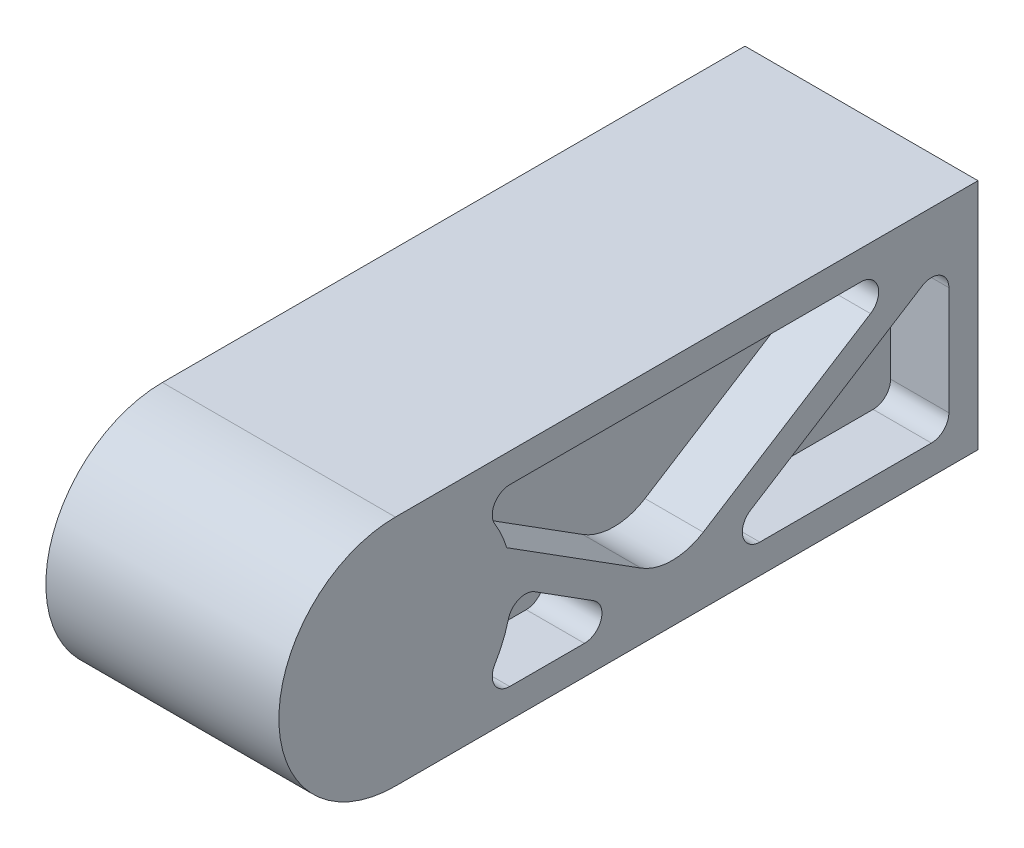
SolidWorks part; units mm, degrees
ref_plane "Front Plane" through (0, 0, 0) normal (0, 0, 1) x (1, 0, 0)
ref_plane "Top Plane" through (0, 0, 0) normal (0, 1, 0) x (1, 0, 0)
ref_plane "Right Plane" through (0, 0, 0) normal (1, 0, 0) x (0, 0, -1)
sketch "Sketch1" plane through (0, 0, 0) normal (1, 0, 0) x (0, 0, -1)
  line L0 (0, 0) -> (-50, 0) construction
  line L1 (-50, -20) -> (50, -20)
  line L2 (-50, -20) -> (-50, 20) construction
  line L3 (-50, 20) -> (50, 20)
  line L4 (50, -20) -> (50, 20)
  line L5 (-50, -20) -> (50, 20) construction
  line L6 (-50, 20) -> (50, -20) construction
  arc A0 (-50, 20) -> (-50, -20) centre (-50, 0) ccw
  point P0 (0, 0)
  point P9 (-47.349, 0)
  dimension "D1" = 100
  dimension "D2" = 40
extrude "Boss-Extrude1" add sketch "Sketch1" along normal blind 20 and the other way blind 20
sketch "Sketch2" plane through (20, 0, 0) normal (1, 0, 0) x (0, 0, -1)
  line L3 (45, 15) -> (-2.5, -15)
  line L4 (-2.5, -15) -> (-50, 15)
  line L5 (43.665, 17.1137) -> (-2.5, -12.0431)
  line L6 (45, -15) -> (45, 15)
  line L7 (-50, -15) -> (45, -15)
  line L8 (45, 15) -> (-50, 15)
  line L9 (45, -15) -> (45, 15)
  line L10 (-50, -15) -> (45, -15)
  line L11 (45, 15) -> (-50, 15)
  line L12 (-2.5, -12.0431) -> (-48.665, 17.1137)
  line L13 (46.335, 12.8863) -> (-2.5, -17.9569)
  line L14 (-2.5, -17.9569) -> (-51.335, 12.8863)
  circle A0 centre (-50, 0) radius 20
  dimension "D1" = 5
  dimension "D2" = 2.5
  dimension "D3" = 2.5
extrude "Cut-Extrude1" cut sketch "Sketch2" against normal blind 10 contours A0 L12 L5 L11 | L9 L13 L10 | A0 L10 L14 region at (20, -5.9856, -30.7272) region at (20, 5.754, 1.1181) region at (20, -10.3863, 23.9176)
sketch "Sketch4" plane through (-20, 0, 0) normal (-1, 0, 0) x (0, 0, 1)
  line L2 (7.1817, -15) -> (36.7712, -15)
  line L3 (2.5, -12.0431) -> (30.8852, 5.8844)
  line L4 (-40.3183, 15) -> (2.5, -12.0431)
  line L5 (36.7712, 15) -> (-40.3183, 15)
  line L6 (2.5, -12.0431) -> (30.8852, 5.8844)
  line L7 (-40.3183, 15) -> (2.5, -12.0431)
  line L8 (36.7712, 15) -> (-40.3183, 15)
  line L9 (30.0085, -0.5831) -> (7.1817, -15)
  line L10 (7.1817, -15) -> (36.7712, -15)
  line L11 (30.0085, -0.5831) -> (7.1817, -15)
  line L13 (-45, 12.0431) -> (-45, -15)
  line L14 (-2.1817, -15) -> (-45, 12.0431)
  line L15 (-45, -15) -> (-2.1817, -15)
  line L16 (-45, 12.0431) -> (-45, -15)
  line L17 (-2.1817, -15) -> (-45, 12.0431)
  line L18 (-45, -15) -> (-2.1817, -15)
  arc A1 (36.7712, 15) -> (30.8852, 5.8844) centre (50, 0) ccw
  arc A2 (36.7712, 15) -> (30.8852, 5.8844) centre (50, 0) ccw
  arc A3 (30.0085, -0.5831) -> (36.7712, -15) centre (50, 0) ccw
  arc A4 (30.0085, -0.5831) -> (36.7712, -15) centre (50, 0) ccw
  dimension "D1" = 0
  dimension "D2" = 0
  dimension "D3" = 0
extrude "Cut-Extrude3" cut sketch "Sketch4" against normal blind 10
fillet "Fillet1" radius 3 16 edges at (-15, -0.5831, 30.0085) (-15, -15, 7.1817) (-15, -15, 36.7712) (-15, -15, -2.1817) (-15, -15, -45) (-15, 12.0431, -45) (-15, 15, -40.3183) (-15, 15, 36.7712) (15, -15, 36.7712) (15, -0.5831, 30.0085) (15, -15, 7.1817) (15, -15, -2.1817) (15, -15, -45) (15, 12.0431, -45) (15, 15, -40.3183) (15, 15, 36.7712)
fillet "Fillet2" radius 10 2 edges at (15, -12.0431, 2.5) (-15, -12.0431, 2.5)
